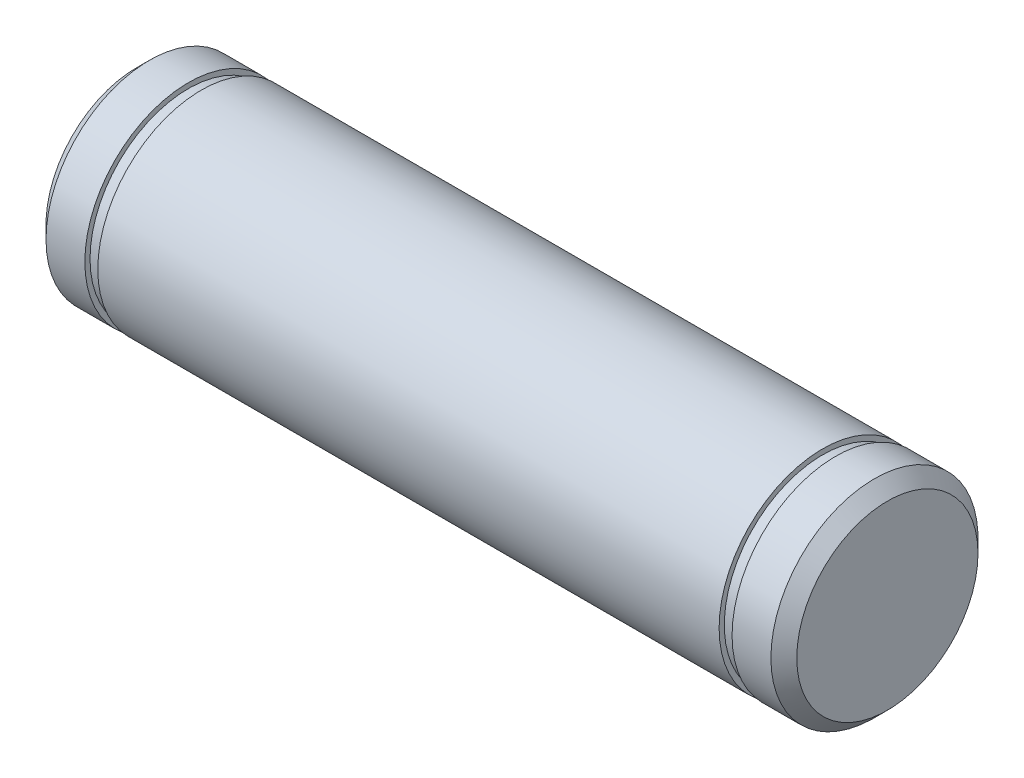
SolidWorks part; units mm, degrees
ref_plane "Front" through (0, 0, 0) normal (0, 0, 1) x (1, 0, 0)
ref_plane "Top" through (0, 0, 0) normal (0, 1, 0) x (1, 0, 0)
ref_plane "Right" through (0, 0, 0) normal (1, 0, 0) x (0, 0, -1)
sketch "Sketch1" plane through (0, 0, 0) normal (1, 0, 0) x (0, 0, -1)
  circle A0 centre (0, 0) radius 2
  dimension "D1" = 4
extrude "Boss-Extrude1" add sketch "Sketch1" along normal blind 14.5
sketch "Sketch2" plane through (14.5, 0, 0) normal (1, 0, 0) x (0, 0, -1)
  circle A0 centre (0, 0) radius 1.9
  circle A1 centre (0, 0) radius 2.4981
  dimension "D1" = 3.8
extrude "Cut-Extrude2" cut sketch "Sketch2" against normal blind 0.25 from offset 1 offset against normal yes
sketch "Sketch3" plane through (0, 0, 0) normal (-1, 0, 0) x (0, 0, 1)
  circle A0 centre (0, 0) radius 1.9
  circle A1 centre (0, 0) radius 2.5
extrude "Cut-Extrude3" cut sketch "Sketch3" against normal blind 0.25 from offset 1 offset against normal yes
chamfer "Chamfer1" distance 0.25 angle 45 2 edges at (14.5, 0, -2) (0, 0, -2)
